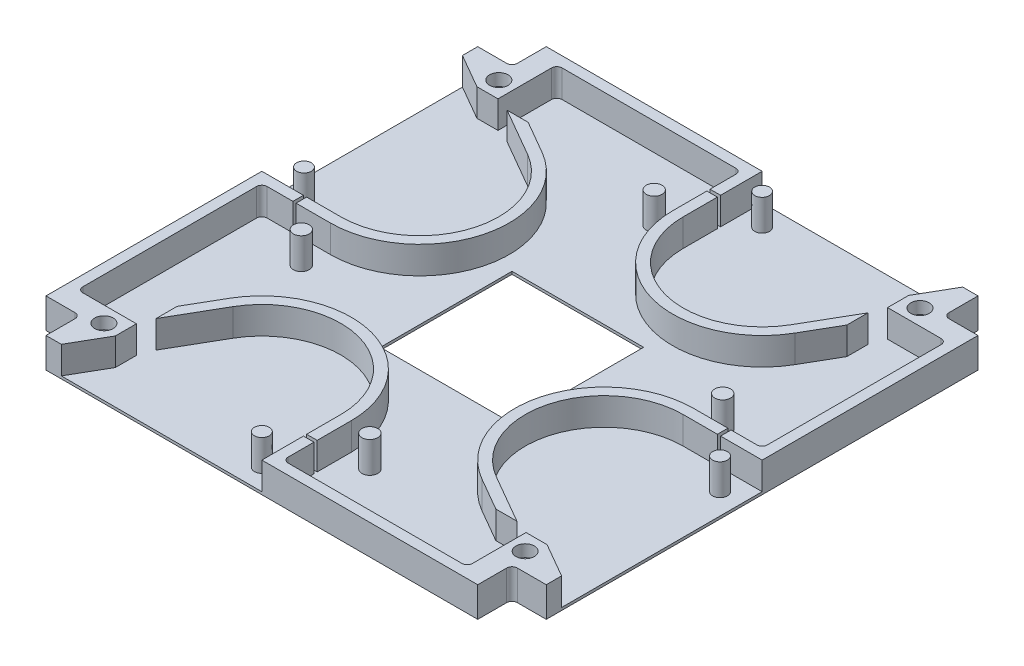
SolidWorks part; units mm, degrees
material "7075-T6 (SN)"
ref_plane "Front Plane" through (0, 0, 0) normal (0, 0, 1) x (1, 0, 0)
ref_plane "Top Plane" through (0, 0, 0) normal (0, 1, 0) x (1, 0, 0)
ref_plane "Right Plane" through (0, 0, 0) normal (1, 0, 0) x (0, 0, -1)
sketch "Sketch1" plane through (0, 0, 0) normal (0, 1, 0) x (1, 0, 0)
  line L0 (0, 0) -> (0, 6.51)
  line L21 (0, 6.51) -> (82, 6.51)
  line L22 (82, 6.51) -> (82, 0)
  line L23 (82, 0) -> (88.51, 0)
  line L24 (88.51, 0) -> (88.51, -82)
  line L25 (88.51, -82) -> (82, -82)
  line L26 (82, -82) -> (82, -88.51)
  line L27 (82, -88.51) -> (0, -88.51)
  line L28 (0, -88.51) -> (0, -82)
  line L29 (0, -82) -> (-6.51, -82)
  line L30 (-6.51, -82) -> (-6.51, 0)
  line L31 (-6.51, 0) -> (0, 0)
  dimension "D1" = 82
  dimension "D2" = 6.51
extrude "Boss-Extrude1" add sketch "Sketch1" along normal blind 0.5
sketch "Sketch2" plane through (0, 0.5, 0) normal (0, 1, 0) x (1, 0, 0)
  line L0 (-6.51, 0) -> (-6.51, -82) construction
  line L1 (0, 6.51) -> (41, 6.51)
  line L2 (0, 6.51) -> (0, 4.51)
  line L3 (0, 4.51) -> (41, 4.51)
  line L4 (41, 6.51) -> (41, 4.51)
  line L5 (88.51, 0) -> (86.51, 0)
  line L6 (88.51, 0) -> (88.51, -41)
  line L7 (88.51, -41) -> (86.51, -41)
  line L8 (86.51, 0) -> (86.51, -41)
  line L9 (82, -88.51) -> (41, -88.51)
  line L10 (82, -88.51) -> (82, -86.51)
  line L11 (82, -86.51) -> (41, -86.51)
  line L12 (41, -88.51) -> (41, -86.51)
  line L13 (-6.51, -82) -> (-4.51, -82)
  line L14 (-6.51, -82) -> (-6.51, -41)
  line L15 (-6.51, -41) -> (-4.51, -41)
  line L16 (-4.51, -82) -> (-4.51, -41)
  line L17 (-6.51, -82) -> (0, -82) construction
  line L18 (41, -8.49) -> (41, 24.5303) construction
  line L19 (56, 6.51) -> (0, 6.51) construction
  line L20 (82, 6.51) -> (0, 6.51) construction
  line L21 (79.094, 6.51) -> (75.3355, 0)
  line L22 (79.094, 6.51) -> (82, 6.51)
  line L23 (82, 6.51) -> (82, 0)
  line L24 (82, 0) -> (86.51, 0)
  line L25 (41, 4.51) -> (41, -8.49)
  line L26 (86.51, -4) -> (75.3355, -4)
  line L27 (39, 4.51) -> (39, -8.49)
  line L28 (72.9929, -8) -> (73.0261, -8)
  line L29 (74.3355, -10.7321) -> (70.7224, -16.99)
  line L31 (75.3355, -4) -> (75.3355, 0)
  line L32 (74.3355, -6.7321) -> (74.3355, -10.7321)
  line L33 (74.3355, -6.7321) -> (68.9904, -15.99)
  circle A0 centre (56, -8.49) radius 15
  circle A1 centre (56, -8.49) radius 17 construction
  arc A2 (70.7224, -16.99) -> (39, -8.49) centre (56, -8.49) cw
  line M24 (88.51, -82) -> (88.51, 0)
  line M25 (88.51, 0) -> (82, 0)
  line M26 (82, 0) -> (82, 6.51)
  line M27 (82, 6.51) -> (0, 6.51)
  line M28 (0, 6.51) -> (0, 0)
  dimension "D3" = 30
  dimension "D6" = 34
  dimension "D1" = 41
  dimension "D2" = 2
  dimension "D7" = 4
  dimension "D8" = 4
  dimension "D5" = 0
  dimension "D9" = 1
  dimension "D4" = 30
  dimension "D10" = 6.6645
  dimension "D11" = 30
  dimension "D12" = 4
extrude "Boss-Extrude2" add sketch "Sketch2" along normal blind 5.2 contours L4 L3 M27 M28 | A2 L28 A0 L25 L3 L27 | L8 L7 M25 M24 | L26 L8 M25 M26 M27 region at (80.332, 0.5, 0.0167) region at (20.5, 0.5, -5.51) region at (40.5365, 0.5, 1.99) region at (87.51, 0.5, 20.5)
sketch "Sketch3" [suppressed] plane through (0, 0.5, 0) normal (0, 1, 0) x (1, 0, 0)
  line L0 (35.5217, -6.4679) -> (39.51, -26.4679)
  line L1 (39.51, -26.4679) -> (39.51, -29.4679)
  line L2 (39.51, -29.4679) -> (79.51, -29.4679)
  line L3 (79.51, -29.4679) -> (79.51, -26.4679)
  line L4 (79.51, -26.4679) -> (83.4983, -6.4679)
  line L6 (35.5217, -6.4679) -> (39.5217, -6.4679)
  line L7 (83.4983, -6.4679) -> (79.4983, -6.4679)
  line L9 (89.51, -41) -> (89.51, 0) construction
  arc A0 (79.4983, -6.4679) -> (39.5217, -6.4679) centre (59.51, -5.7836) cw
  circle A1 centre (58.485, 0) radius 15 construction
  dimension "D3" = 20
  dimension "D7" = 30
  dimension "D1" = 3
  dimension "D2" = 4
  dimension "D4" = 20
  dimension "D5" = 40
  dimension "D6" = 10
extrude "Boss-Extrude3" [suppressed] add sketch "Sketch3" along normal blind 6
ref_plane "Plane1" through (41, 0, 41) normal (0.7071, 0, 0.7071) x (0.7071, 0, -0.7071)
ref_plane "Plane2" through (0, 0, 0) normal (0.7071, 0, -0.7071) x (-0.7071, 0, -0.7071)
ref_axis "Axis1" through (41, -0.325, 41) along (0, 1, 0)
pattern_circular "CirPattern1" count 4 every 90 about axis through (41, -0.325, 41) along (0, 1, 0) of "Boss-Extrude2"
sketch "Sketch4" plane through (0, 0, 0) normal (0, -1, 0) x (1, 0, 0)
  line L0 (78, -6.51) -> (78, -0.51) construction
  line L1 (82, -6.51) -> (0, -6.51) construction
  line L2 (82, 0) -> (82, -6.51) construction
  line L3 (88.51, 78) -> (82.51, 78) construction
  line L4 (88.51, 82) -> (88.51, 0) construction
  line L5 (4, 88.51) -> (4, 82.51) construction
  line L6 (0, 88.51) -> (82, 88.51) construction
  line L7 (-6.51, 4) -> (-0.51, 4) construction
  line L8 (-6.51, 0) -> (-6.51, 82) construction
  line L10 (82, 82) -> (88.51, 82) construction
  line L11 (0, 82) -> (0, 88.51) construction
  line L12 (0, 0) -> (-6.51, 0) construction
  point P7 (78, -0.51)
  dimension "D1" = 6
  dimension "D2" = 4
  dimension "D3" = 4
  dimension "D4" = 4
  dimension "D5" = 4
  dimension "D6" = 6
  dimension "D7" = 6
  dimension "D8" = 6
sketch "Sketch8" plane through (0, 0.5, 0) normal (0, 1, 0) x (1, 0, 0)
  line L0 (2.906, -88.51) -> (41, -88.51) construction
  line L1 (41, -88.51) -> (41, -73.51) construction
  circle A0 centre (37, -84.51) radius 1.4
  dimension "D1" = 2.8
  dimension "D2" = 4
  dimension "D3" = 4
extrude "Boss-Extrude4" add sketch "Sketch8" along normal blind 5.9
pattern_circular "CirPattern2" count 4 every 90 about axis through (41, -0.325, 41) along (0, 1, 0) of "Boss-Extrude4"
fillet "Fillet1" radius 1 8 edges at (-4.51, 3.1, 78) (-4.51, 3.1, 43) (4, 3.1, -4.51) (39, 3.1, -4.51) (86.51, 3.1, 4) (86.51, 3.1, 39) (78, 3.1, 86.51) (43, 3.1, 86.51)
sketch "Sketch11" plane through (0, 0.5, 0) normal (0, 1, 0) x (1, 0, 0)
  line L0 (53.5, -53.5) -> (53.5, -28.5)
  line L1 (53.5, -28.5) -> (28.5, -28.5)
  line L2 (28.5, -28.5) -> (28.5, -53.5)
  line L3 (28.5, -53.5) -> (53.5, -53.5)
  line L5 (79.094, 6.51) -> (41, 6.51) construction
  line L6 (-6.51, -2.906) -> (-6.51, -41) construction
  dimension "D1" = 25
  dimension "D2" = 25
  dimension "D3" = 35.01
  dimension "D4" = 35.01
extrude "Cut-Extrude2" cut sketch "Sketch11" against normal through all
sketch "Sketch14" plane through (0, 6.4, 0) normal (0, 1, 0) x (1, 0, 0)
  point P0 (37, -84.51)
sketch "Sketch15" plane through (0, 5.7, 0) normal (0, 1, 0) x (1, 0, 0)
  line L0 (82, -82) -> (88.51, -82) construction
  line L2 (78, -85.51) -> (78, -75.3355) construction
  circle A0 centre (81, -78.5) radius 0.9
  circle A1 centre (78.5, -1) radius 0.9
  circle A2 centre (1, -3.5) radius 0.9
  circle A3 centre (3.5, -81) radius 0.9
  point P0 (1, -3.5)
  point P1 (1, -3.5)
  point P2 (3.5, -81)
  point P3 (81, -78.5)
  point P4 (78.5, -1)
  point P5 (3.5, -81)
  dimension "D3" = 1.8
  dimension "D4" = 1.8
  dimension "D5" = 1.8
  dimension "D6" = 1.8
  dimension "D1" = 3.5
  dimension "D2" = 3
extrude "Cut-Extrude3" cut sketch "Sketch15" against normal through all
sketch "Sketch16" plane through (0, 5.7, 0) normal (0, 1, 0) x (1, 0, 0)
  circle A0 centre (78.5, -1) radius 1.75
  circle A1 centre (81, -78.5) radius 1.75
  circle A2 centre (3.5, -81) radius 1.75
  circle A3 centre (1, -3.5) radius 1.75
  dimension "D1" = 3.5
  dimension "D2" = 3.5
  dimension "D3" = 3.5
  dimension "D4" = 3.5
extrude "Cut-Extrude4" cut sketch "Sketch16" against normal blind 2.3
hole_wizard "CBORE for M1.6 SHCS2" positions "3DSketch2" profile "Sketch18" counterbore size "M1.6" standard "ANSI Metric" end condition through all
sketch3d "3DSketch2"
  line L0 (81, 0, 78.5) -> (81, 3.4, 78.5) construction
  line L1 (78.5, 0, 1) -> (78.5, 3.4, 1) construction
  line L2 (1, 0, 3.5) -> (1, 3.4, 3.5) construction
  line L3 (3.5, 0, 81) -> (3.5, 3.4, 81) construction
  point P0 (81, 0, 78.5)
  point P4 (78.5, 0, 1)
  point P8 (1, 0, 3.5)
  point P12 (3.5, 0, 81)
sketch "Sketch18" plane through (81, 0, 78.5) normal (1, 0, 0) x (0, 0, -1)
  line L0 (0, 0) -> (0, 6.4)
  line L1 (0, 6.4) -> (0.9, 6.4)
  line L3 (0.9, 6.4) -> (0.9, 1.6)
  line L4 (0.9, 1.6) -> (1.75, 1.6)
  line L5 (1.75, 1.6) -> (1.75, 0)
  line L7 (1.75, 0) -> (0, 0)
  line L11 (0, -6.35) -> (0, 107.95) construction
  dimension "Thru Hole Dia." = 1.8
  dimension "Thru Hole Depth" = 6.4
  dimension "C'Bore Dia." = 3.5
  dimension "C'Bore Depth" = 1.6
sketch "Sketch20" plane through (0, 5.7, 0) normal (0, 1, 0) x (1, 0, 0)
  line L0 (80.61, -39) -> (80.61, -41)
  line L1 (85.51, -39) -> (73.51, -39) construction
  line L2 (88.51, -41) -> (73.51, -41) construction
  line L3 (80.61, -41) -> (80.01, -41)
  line L4 (80.01, -41) -> (80.01, -39)
  line L5 (80.01, -39) -> (80.61, -39)
  circle A0 centre (84.51, -45) radius 1.4 construction
  dimension "D1" = 3.9
  dimension "D2" = 4.5
sketch "Sketch24" plane through (0, 0.5, 0) normal (0, 1, 0) x (1, 0, 0)
  point P0 (41, -41)
  dimension "D1" = 41
  dimension "D2" = 41
extrude "Cut-Extrude6" cut sketch "Sketch20" against normal up to surface (5.2 mm away) up to face at (41, 0.5, 41)
pattern_circular "CirPattern3" count 4 over 360 about axis through (41, -0.325, 41) along (0, 1, 0) of "Cut-Extrude6"
fillet "Fillet2" radius 1 4 edges at (0, 2.85, 0) (82, 2.85, 0) (82, 2.85, 82) (0, 2.85, 82)
sketch "Sketch25" plane through (0, 0.5, 0) normal (0, 1, 0) x (1, 0, 0)
  line L1 (79.094, 6.51) -> (41, 6.51) construction
  line L2 (88.51, -41) -> (88.51, 0) construction
  circle A0 centre (74.51, -34.49) radius 1.5
  point P0 (74.51, -34.49)
  dimension "D2" = 3
  dimension "D1" = 41
  dimension "D3" = 14
extrude "Boss-Extrude5" add sketch "Sketch25" along normal blind 5.9
pattern_circular "CirPattern4" count 4 over 360 about axis through (41, -0.325, 41) along (0, 1, 0) of "Boss-Extrude5"
equation "\"D6@Sketch2\"=\"D3@Sketch2\"+4"
equation "\"D3@Sketch4\"=\"D2@Sketch4\""
equation "\"D4@Sketch4\"=\"D3@Sketch4\""
equation "\"D5@Sketch4\"=\"D4@Sketch4\""
equation "\"D6@Sketch4\"=\"D1@Sketch4\""
equation "\"D7@Sketch4\"=\"D6@Sketch4\""
equation "\"D8@Sketch4\"=\"D7@Sketch4\""
